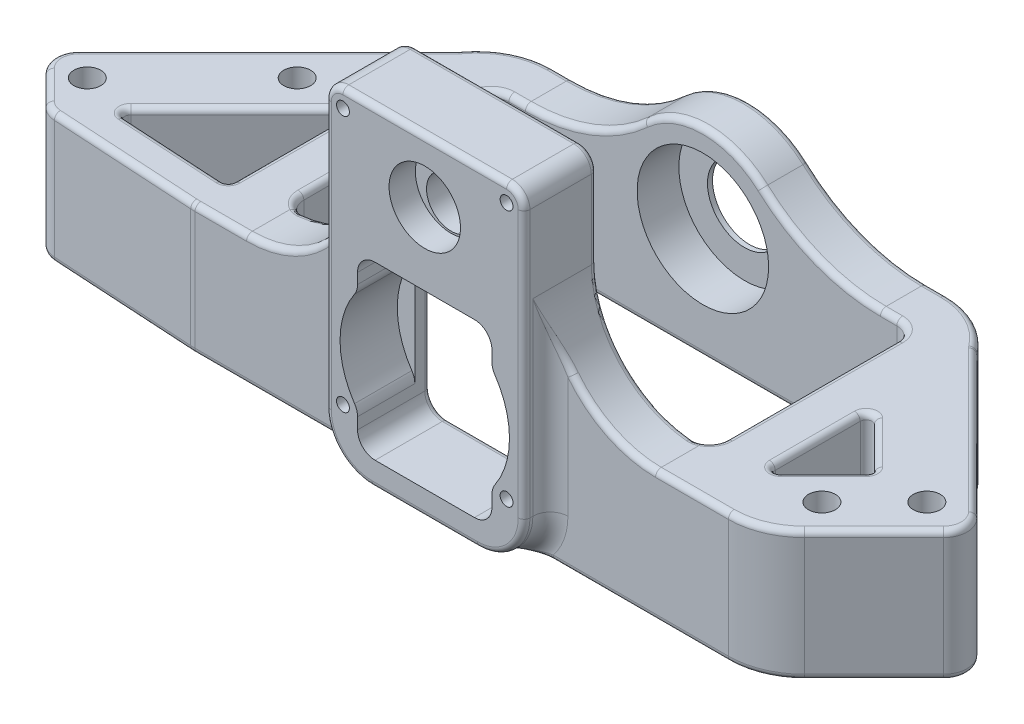
SolidWorks part; units mm, degrees
ref_plane "Front Plane" through (0, 0, 0) normal (0, 0, 1) x (1, 0, 0)
ref_plane "Top Plane" through (0, 0, 0) normal (0, 1, 0) x (1, 0, 0)
ref_plane "Right Plane" through (0, 0, 0) normal (1, 0, 0) x (0, 0, -1)
sketch "Sketch1" plane through (0, 0, 0) normal (0, 1, 0) x (1, 0, 0)
  line L0 (-44.195, -25.55) -> (-44.195, 25.55)
  line L1 (36.195, -17.55) -> (-36.195, -17.55)
  line L2 (36.195, -17.55) -> (36.195, 17.55)
  line L3 (36.195, 17.55) -> (-36.195, 17.55)
  line L4 (-36.195, -17.55) -> (-36.195, 17.55)
  line L5 (36.195, -17.55) -> (-36.195, 17.55) construction
  line L6 (36.195, 17.55) -> (-36.195, -17.55) construction
  line L11 (44.195, 25.55) -> (-44.195, 25.55)
  line L12 (44.195, -25.55) -> (44.195, 25.55)
  line L13 (44.195, -25.55) -> (-44.195, -25.55)
  line L14 (-79.6522, -15.223) -> (-70.8875, -23.9877)
  line L15 (-70.8875, -23.9877) -> (-44.195, 2.7047)
  line L16 (-79.6522, -15.223) -> (-44.195, 20.2342)
  line L17 (0, 0) -> (0, 65.6417) construction
  line L18 (-75.3776, -19.4976) -> (0, 55.88) construction
  line L19 (-44.195, -25.55) -> (-70.8875, -23.9877)
  line L20 (-44.195, -19.5397) -> (-65.2095, -18.3098)
  line L21 (0, 55.88) -> (62.8618, -6.9818) construction
  line L22 (62.8618, -6.9818) -> (53.8815, -15.962) construction
  line L23 (52.8428, -25.55) -> (71.411, -6.9818)
  line L24 (71.411, -6.9818) -> (44.195, 20.2342)
  line L25 (52.8428, -25.55) -> (44.195, -25.55)
  line L26 (-75.3776, -19.4976) -> (-269.4077, -213.5277) construction
  line L27 (44.195, 2.7047) -> (53.8815, -6.9818)
  line L28 (53.8815, -6.9818) -> (44.195, -16.6683)
  circle A0 centre (-71.842, -15.962) radius 2.3
  circle A1 centre (-53.8815, 1.9985) radius 2.3
  circle A6 centre (62.8618, -6.9818) radius 2.3
  circle A7 centre (53.8815, -15.962) radius 2.3
  point P0 (0, 0)
  point P21 (-75.3776, -19.4976)
  point P32 (-197.5656, -141.6856)
  point P34 (-215.5261, -159.6461)
  point P37 (52.7429, -25.55)
  dimension "D10" = 4.6
  dimension "D24" = 4.6
  dimension "D1" = 8
  dimension "D2" = 45
  dimension "D3" = 55.88
  dimension "D4" = 5
  dimension "D5" = 76.2
  dimension "D6" = 12.3952
  dimension "D7" = 25.4
  dimension "D8" = 72.39
  dimension "D9" = 35.1
  dimension "D11" = 6
  dimension "D12" = 381
  dimension "D13" = 101.6
  dimension "D14" = 177.8
  dimension "D15" = 25.4
  dimension "D16" = 228.6
  dimension "D17" = 6.35
  dimension "D18" = 88.9
  dimension "D19" = 12.7
  dimension "D20" = 12.3952
  dimension "D21" = 6.35
  dimension "D22" = 12.3952
  dimension "D23" = 6.35
extrude "Boss-Extrude1" add sketch "Sketch1" along normal blind 22.25 contours L13 L12 L11 L0 L1 L4 L3 L2 | L27 L28 L12 L25 L23 L24 A7 A6 | L0 L20 L15 L19 | L16 L14 L15 L0 A1 A0 region at (-56.1781, 0, 21.9627) region at (-43.174, 0, 22.5449) region at (54.3256, 0, 5.3309) region at (-59.6388, 0, 3.5495)
extrude "Boss-Extrude2" add sketch "Sketch1<3>" along normal blind 15.85 from surface contours L13 L12 L11 L0 L1 L4 L3 L2 region at (-43.174, 0, 22.5449) starting at face at (-51.1998, 22.25, 11.7149)
sketch "Sketch1<3>" plane through (0, 0, 0) normal (0, 1, 0) x (1, 0, 0) same geometry as "Sketch1"
sketch "Sketch3" plane through (0, 0, 25.55) normal (0, 0, 1) x (1, 0, 0)
  line L0 (0, 0) -> (0, 38.1) construction
  line L1 (-44.195, 38.1) -> (44.195, 38.1) construction
  line L13 (-44.195, 22.25) -> (-17, 22.25)
  line L14 (-17, 22.25) -> (-17, 56.7)
  line L15 (-17, 56.7) -> (17, 56.7)
  line L16 (17, 56.7) -> (17, 22.25)
  line L17 (17, 22.25) -> (44.195, 22.25)
  line L18 (44.195, 38.1) -> (44.195, 22.25) construction
  line L19 (44.195, 22.25) -> (44.195, 38.1)
  line L20 (44.195, 38.1) -> (17, 38.1)
  line L21 (-17, 38.1) -> (-44.195, 38.1)
  line L22 (-44.195, 38.1) -> (-44.195, 22.25)
  line L23 (-17, 38.1) -> (17, 38.1)
  line L24 (11.5, 33.65) -> (-11.5, 33.65)
  line L25 (-11.5, 33.65) -> (-11.5, 27.8818)
  line L26 (11.5, 33.65) -> (11.5, 27.8818)
  line L27 (-44.195, 22.25) -> (-70.8875, 22.25) construction
  line L28 (52.8428, 0) -> (-44.195, 0) construction
  line L29 (11.5, 4.3) -> (-11.5, 4.3)
  line L30 (-11.5, 4.3) -> (-11.5, 10.2182)
  line L31 (11.5, 4.3) -> (11.5, 10.2182)
  line L32 (-11.5, 27.8818) -> (-11.5, 10.2182)
  line L33 (11.5, 27.8818) -> (11.5, 10.2182)
  circle A0 centre (14, 9.8) radius 1.1
  circle A1 centre (-14, 9.8) radius 1.1
  circle A2 centre (-14, 53.7) radius 1.1
  circle A3 centre (14, 53.7) radius 1.1
  circle A4 centre (0, 46.05) radius 6.114
  circle A20 centre (0, 44.45) radius 4.2
  circle A21 centre (0, 19.05) radius 14.5
  point P5 (0, 19.05)
  point P10 (0, 33.65)
  point P17 (0, 19.05)
  point P19 (0, 4.3)
  point P90 (-44.195, 22.25)
  line M46 (44.195, 22.25) -> (44.195, 38.1)
  line M47 (44.195, 38.1) -> (-44.195, 38.1)
  line M48 (-44.195, 38.1) -> (-44.195, 22.25)
  dimension "D1" = 2.2
  dimension "D5" = 12.228
  dimension "D6" = 8.4
  dimension "D8" = 1.6
  dimension "D14" = 34
  dimension "D15" = 29
  dimension "D2" = 3
  dimension "D3" = 3
  dimension "D4" = 3
  dimension "D7" = 25.4
  dimension "D9" = 28
  dimension "D10" = 43.9
  dimension "D11" = 34.45
  dimension "D12" = 27.195
  dimension "D13" = 19.05
  dimension "D16" = 23
  dimension "D17" = 14.6
  dimension "D18" = 14.75
extrude "Boss-Extrude3" add sketch "Sketch3" against normal up to surface (8 mm away) contours L16 L15 L14 L23 A4 A3 A2 M47 region at (-16.6124, 47.4, 25.55) up to face at (0, 19.05, 17.55)
extrude "Cut-Extrude1" cut sketch "Sketch3<3>" against normal up to next contours L13 L14 M47 M48 | L16 L17 M46 M47 region at (-30.5975, 30.175, 25.55) region at (30.5975, 30.175, 25.55)
sketch "Sketch3<3>" plane through (0, 0, 25.55) normal (0, 0, 1) x (1, 0, 0) same geometry as "Sketch3"
extrude "Cut-Extrude2" cut sketch "Sketch3<4>" against normal up to next contours L0 A21 | A21 L0 | L29 L0 A21 L30 | L0 L29 L31 A21 | L0 A21 L26 L24 | A21 L0 L24 L25 | A0 | A1 | L32 A21 | L33 A21 region at (-8.3672, 5.9503, 25.55) region at (8.3672, 5.9503, 25.55) region at (-5.3485, 19.05, 25.55) region at (5.3485, 19.05, 25.55) region at (-8.5839, 32.0193, 25.55) region at (8.5839, 32.0193, 25.55) region at (-12.7113, 19.05, 25.55) region at (12.7113, 19.05, 25.55) region at (14, 9.8, 25.55) region at (-14, 9.8, 25.55)
sketch "Sketch3<4>" plane through (0, 0, 25.55) normal (0, 0, 1) x (1, 0, 0) same geometry as "Sketch3"
sketch "Sketch4" plane through (0, 0, -25.55) normal (0, 0, -1) x (-1, 0, 0)
  line L0 (0, 0) -> (0, 38.1) construction
  line L1 (17, 38.1) -> (-17, 38.1) construction
  line L5 (-17, 22.25) -> (-14.6547, 22.25)
  line L6 (-17, 22.25) -> (-17, 38.1)
  line L7 (-17, 38.1) -> (17, 38.1)
  line L8 (17, 38.1) -> (17, 22.25)
  line L9 (17, 22.25) -> (14.6547, 22.25)
  circle A0 centre (0, 19.05) radius 6.35
  circle A1 centre (0, 19.05) radius 15
  line M7 (17, 22.25) -> (17, 38.1)
  line M8 (17, 38.1) -> (-17, 38.1)
  line M9 (-17, 38.1) -> (-17, 22.25)
  dimension "D1" = 30
  dimension "D2" = 12.7
extrude "Cut-Extrude3" cut sketch "Sketch4" against normal up to next contours A1 L0 L7 L5 M9 | L0 A1 L9 M7 M8 | L0 A0 | A0 L0 region at (2.695, 19.05, -25.55) region at (-2.695, 19.05, -25.55) region at (10.8276, 32.9317, -25.55) region at (-10.8276, 32.9317, -25.55)
extrude "Boss-Extrude6" add sketch "Sketch3<7>" along normal blind 2.7 from surface contours L32 A21 | L33 A21 region at (12.7113, 19.05, 25.55) region at (-12.7113, 19.05, 25.55) starting at face at (-12.9, 9.8, 17.55)
sketch "Sketch3<7>" plane through (0, 0, 25.55) normal (0, 0, 1) x (1, 0, 0) same geometry as "Sketch3"
sketch "Sketch9" plane through (0, 0, 25.55) normal (0, 0, 1) x (1, 0, 0)
  line L0 (-17, 22.25) -> (-17, 0)
  line L1 (17, 22.25) -> (17, 0)
  line L6 (-11.5, 33.65) -> (-11.5, 27.8818)
  line L7 (11.5, 33.65) -> (-11.5, 33.65)
  line L8 (11.5, 27.8818) -> (11.5, 33.65)
  line L9 (11.5, 4.3) -> (11.5, 10.2182)
  line L10 (-11.5, 4.3) -> (11.5, 4.3)
  line L11 (-11.5, 10.2182) -> (-11.5, 4.3)
  line L12 (-11.5, 33.65) -> (-11.5, 27.8818)
  line L13 (11.5, 33.65) -> (-11.5, 33.65)
  line L14 (11.5, 27.8818) -> (11.5, 33.65)
  line L15 (11.5, 4.3) -> (11.5, 10.2182)
  line L16 (-11.5, 4.3) -> (11.5, 4.3)
  line L17 (-11.5, 10.2182) -> (-11.5, 4.3)
  line L20 (-17, 22.25) -> (-44.195, 22.25)
  line L21 (-44.195, 22.25) -> (-44.195, 0)
  line L22 (-44.195, 0) -> (52.8428, 0)
  line L23 (52.8428, 0) -> (52.8428, 22.25)
  line L24 (52.8428, 22.25) -> (17, 22.25)
  line L25 (17, 22.25) -> (17, 56.7)
  line L26 (17, 56.7) -> (-17, 56.7)
  line L27 (-17, 56.7) -> (-17, 22.25)
  line L28 (-17, 22.25) -> (-44.195, 22.25)
  line L29 (-44.195, 22.25) -> (-44.195, 0)
  line L30 (-44.195, 0) -> (52.8428, 0)
  line L32 (52.8428, 22.25) -> (17, 22.25)
  line L33 (17, 22.25) -> (17, 56.7)
  line L34 (17, 56.7) -> (-17, 56.7)
  line L35 (-17, 56.7) -> (-17, 22.25)
  line L38 (52.8428, 0) -> (52.8428, 22.25)
  circle A1 centre (0, 46.05) radius 6.114
  circle A2 centre (0, 46.05) radius 6.114
  circle A3 centre (14, 53.7) radius 1.1
  circle A4 centre (14, 53.7) radius 1.1
  circle A5 centre (-14, 53.7) radius 1.1
  circle A6 centre (-14, 53.7) radius 1.1
  circle A7 centre (14, 9.8) radius 1.1
  circle A8 centre (14, 9.8) radius 1.1
  circle A9 centre (-14, 9.8) radius 1.1
  arc A10 (11.5, 10.2182) -> (11.5, 27.8818) centre (0, 19.05) ccw
  arc A11 (-11.5, 27.8818) -> (-11.5, 10.2182) centre (0, 19.05) ccw
  arc A12 (11.5, 10.2182) -> (11.5, 27.8818) centre (0, 19.05) ccw
  arc A13 (-11.5, 27.8818) -> (-11.5, 10.2182) centre (0, 19.05) ccw
  circle A14 centre (-14, 9.8) radius 1.1
  circle M22 centre (-14, 9.8) radius 1.1
  line M23 (-11.5, 27.8818) -> (-11.5, 33.65)
  line M24 (-11.5, 33.65) -> (11.5, 33.65)
  line M25 (11.5, 33.65) -> (11.5, 27.8818)
  arc M26 (11.5, 27.8818) -> (11.5, 10.2182) centre (0, 19.05) cw
  line M27 (11.5, 10.2182) -> (11.5, 4.3)
  line M28 (11.5, 4.3) -> (-11.5, 4.3)
  line M29 (-11.5, 4.3) -> (-11.5, 10.2182)
  arc M30 (-11.5, 10.2182) -> (-11.5, 27.8818) centre (0, 19.05) cw
  circle M31 centre (14, 9.8) radius 1.1
  line M34 (-44.195, 0) -> (52.8428, 0)
  line M37 (17, 22.25) -> (17, 56.7)
  line M38 (17, 56.7) -> (-17, 56.7)
  line M39 (-17, 56.7) -> (-17, 22.25)
  circle M40 centre (0, 46.05) radius 6.114
  circle M41 centre (14, 53.7) radius 1.1
  circle M42 centre (-14, 53.7) radius 1.1
  dimension "D1" = 0
  dimension "D2" = 0
  dimension "D3" = 0
  dimension "D4" = 0
  dimension "D5" = 0
  dimension "D6" = 0
  dimension "D7" = 0
extrude "Boss-Extrude7" add sketch "Sketch9" along normal blind 4.5 contours L1 L0 M37 M38 M39 M34 M30 M23 M24 M25 M26 M27 M28 M29 M31 M40 M42 M41 M22 region at (-16.3389, 39.475, 25.55)
fillet "Fillet1" radius 18 2 edges at (17, 22.25, 21.55) (-17, 22.25, 21.55)
fillet "Fillet2" radius 3 2 edges at (-17, 56.7, 23.8) (17, 56.7, 23.8)
fillet "Fillet4" radius 1 6 edges at (-44.195, 11.125, -2.7047) (-44.195, 11.125, 19.5397) (-65.2095, 11.125, 18.3098) (53.8815, 11.125, 6.9818) (44.195, 11.125, 16.6683) (44.195, 11.125, -2.7047)
fillet "Fillet5" radius 3 4 edges at (-36.195, 11.125, -17.55) (36.195, 11.125, -17.55) (36.195, 11.125, 17.55) (-36.195, 11.125, 17.55)
fillet "Fillet6" radius 13 4 edges at (44.195, 11.125, -25.55) (-44.195, 11.125, -25.55) (-44.195, 11.125, 25.55) (52.8428, 11.125, 25.55)
fillet "Fillet7" radius 4 3 edges at (-70.8875, 11.125, 23.9877) (-79.6522, 11.125, 15.223) (71.411, 11.125, 6.9818)
fillet "Fillet12" radius 8 2 edges at (-17, 0, 27.8) (17, 0, 27.8)
sketch "Sketch5" plane through (0, 0, -17.55) normal (0, 0, 1) x (1, 0, 0)
  circle A0 centre (0, 19.05) radius 11.25
  dimension "D1" = 22.5
extrude "Cut-Extrude4" cut sketch "Sketch5" against normal blind 7.1374
fillet "Fillet16" radius 3 4 edges at (14.6569, 2.3431, 25.55) (-14.6569, 2.3431, 25.55) (17, 24.125, 25.55) (-17, 24.125, 25.55)
fillet "Fillet8" radius 30 2 edges at (14.6547, 22.25, -21.55) (-14.6547, 22.25, -21.55)
fillet "Fillet10" radius 2 2 edges at (-44.195, 11.125, -20.2342) (44.195, 11.125, -20.2342)
fillet "Fillet9" radius 1 92 edges at (-34.1764, 22.2689, 17.3849) (-19.5142, 24.2857, -17.55) (0, 34.05, -17.55) (19.5142, 24.2857, -17.55) (35.3163, 22.25, -16.6713) (36.195, 22.25, 0) (35.8797, 22.25, 15.8888) (34.1145, 22.2718, 17.4056) (21.6492, 28.1771, 17.55) (17, 46.975, 17.55) (16.1213, 55.8213, 17.55) (0, 56.7, 17.55) (-16.1213, 55.8213, 17.55) (-17, 46.975, 17.55) (-19.5142, 24.2857, -25.55) (0, 34.05, -25.55) (19.5142, 24.2857, -25.55) (-32.0431, 22.25, -25.55) (-26.4882, 24.3897, 25.55) (-44.195, 22.25, 9.0945) (-35.3163, 0, 16.6713) (0, 0, 17.55) (35.3163, 0, 16.6713) (36.195, 0, 0) (35.3163, 0, -16.6713) (0, 0, -17.55) (-35.3163, 0, -16.6713) (44.195, 0, 6.9818) (-44.195, 0, 9.0945) (-21.6492, 28.1771, 17.55) (-36.195, 0, 0) (0, 0, -25.55) (-39.4074, 22.25, 25.55) (-35.8797, 22.25, 15.8888) (-36.195, 22.25, 0) (-35.3163, 22.25, -16.6713) (-31.786, 22.25, -17.55) (-44.5089, 0, 19.207) (-54.1195, 0, 18.9589) (-63.8618, 0, 17.7972) (-54.7682, 0, 7.8684) (-44.8123, 0, -1.2144) (-44.8123, 22.25, -1.2144) (-54.7682, 22.25, 7.8684) (-63.8618, 22.25, 17.7972) (-54.1195, 22.25, 18.9589) (-44.5089, 22.25, 19.207) (39.5259, 0, -24.1761) (-39.5259, 0, -24.1761) (-60.5616, 0, -3.8676) (-77.9953, 0, 15.223) (-44.1948, 0, 25.5444) (-56.9715, 0, 24.8022) (-70.773, 0, 23.7326) (-60.5616, 22.25, -3.8676) (-77.9953, 22.25, 15.223) (-44.1948, 22.25, 25.5444) (-56.9715, 22.25, 24.8022) (-70.773, 22.25, 23.7326) (-74.3935, 0, 20.4816) (-74.3935, 22.25, 20.4816) (-44.2025, 0, -20.2339) (-44.2025, 22.25, -20.2339) (-39.5259, 22.25, -24.1761) (-30.1824, 0, 25.55) (16.1213, 55.8213, 30.05) (0, 56.7, 30.05) (-16.1213, 55.8213, 30.05) (-17, 30.85, 30.05) (-14.6569, 2.3431, 30.05) (0, 0, 30.05) (14.6569, 2.3431, 30.05) (17, 30.85, 30.05) (14.0902, 0, 25.9624) (-14.0902, 0, 25.9624) (-18.5515, 32.9393, 25.9229) (44.8123, 0, 15.178) (49.5383, 0, 11.3251) (53.4673, 0, 6.9818) (49.5383, 0, 2.6385) (44.8123, 0, -1.2144) (32.0039, 0, 25.55) (52.4329, 0, 24.5604) (62.6165, 0, 15.7763) (69.7541, 0, 6.9818) (56.441, 0, -7.9882) (44.2025, 0, -20.2339) (44.8123, 22.25, -1.2144) (44.8123, 22.25, 15.178) (49.5383, 22.25, 11.3251) (53.4673, 22.25, 6.9818) (49.5383, 22.25, 2.6385)
fillet "Fillet11" radius 3 8 edges at (-11.5, 4.3, 23.8) (11.5, 4.3, 23.8) (11.5, 33.65, 23.8) (-11.5, 33.65, 23.8) (11.5, 27.8818, 25.15) (11.5, 10.2182, 25.15) (-11.5, 27.8818, 25.15) (-11.5, 10.2182, 25.15)
fillet "Fillet14" radius 1 8 edges at (-10.6213, 5.1787, 17.55) (-11.5, 18.975, 17.55) (-10.6213, 32.7713, 17.55) (0, 33.65, 17.55) (10.6213, 32.7713, 17.55) (11.5, 18.975, 17.55) (10.6213, 5.1787, 17.55) (0, 4.3, 17.55)
extrude "Boss-Extrude8" add sketch "Sketch3<8>" against normal up to surface (8 mm away) contours A4 A20 region at (-5.9411, 46.05, 25.55) up to face at (0, 18.975, 17.55)
sketch "Sketch3<8>" plane through (0, 0, 25.55) normal (0, 0, 1) x (1, 0, 0) same geometry as "Sketch3"
